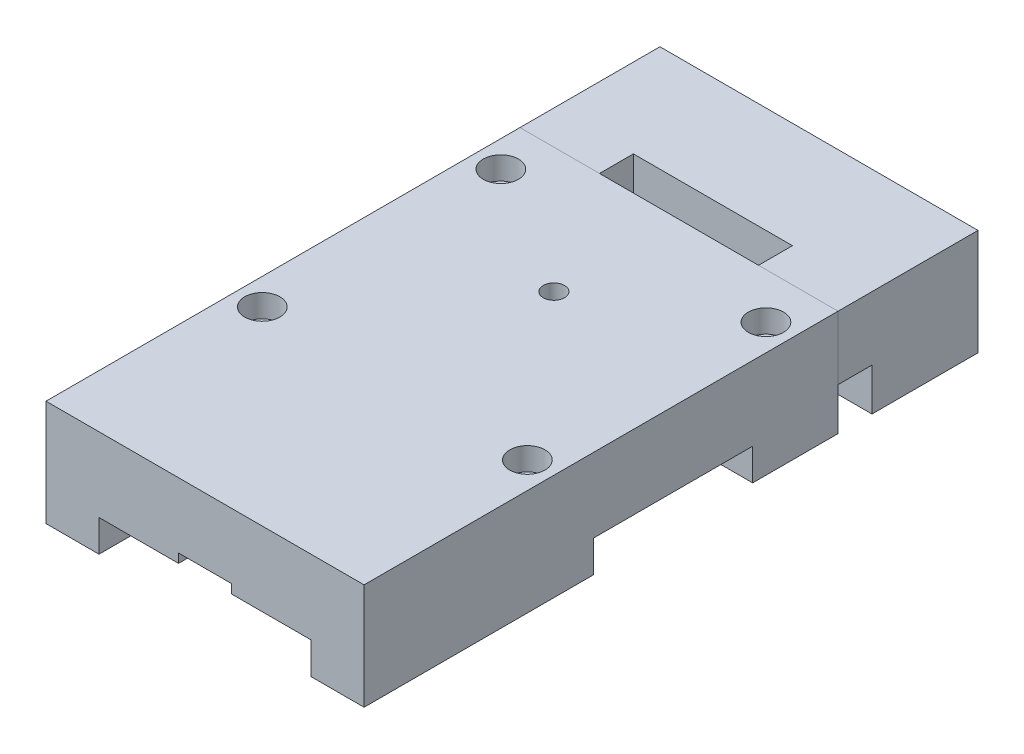
SolidWorks part; units mm, degrees
material "Nylon 6/10"
ref_plane "Front Plane" through (0, 0, 0) normal (0, 0, 1) x (1, 0, 0)
ref_plane "Top Plane" through (0, 0, 0) normal (0, 1, 0) x (1, 0, 0)
ref_plane "Right Plane" through (0, 0, 0) normal (1, 0, 0) x (0, 0, -1)
sketch "Sketch1" plane through (0, 0, 0) normal (0, 1, 0) x (1, 0, 0)
  line L1 (-38.1, -73.533) -> (38.1, -73.533)
  line L2 (-38.1, -73.533) -> (-38.1, 73.533)
  line L3 (-38.1, 73.533) -> (38.1, 73.533)
  line L4 (38.1, -73.533) -> (38.1, 73.533)
  line L5 (-38.1, -73.533) -> (38.1, 73.533) construction
  line L6 (-38.1, 73.533) -> (38.1, -73.533) construction
  point P0 (0, 0)
  dimension "D1" = 76.2
  dimension "D2" = 147.066
extrude "Boss-Extrude1" add sketch "Sketch1" along normal blind 12.7 and the other way blind 12.7
sketch "Sketch2" plane through (0, 0, -73.533) normal (0, 0, -1) x (-1, 0, 0)
  line L1 (-38.1, -12.7) -> (38.1, -12.7) construction
  circle A0 centre (0, -12.7) radius 4.7625
  dimension "D1" = 9.525
extrude "Cut-Extrude1" cut sketch "Sketch2" against normal blind 25.4
ref_plane "Plane1" through (0, -12.7, 0) normal (0, -1, 0) x (-1, 0, 0)
sketch "Sketch3" plane through (0, -12.7, 0) normal (0, -1, 0) x (-1, 0, 0)
  line L0 (10.922, 19.558) -> (44.45, 19.558)
  line L1 (-19.05, -83.058) -> (19.05, -83.058)
  line L2 (-25.4, -76.708) -> (-25.4, -18.542)
  line L3 (0, 0) -> (0, 102.0916) construction
  line L4 (25.4, -76.708) -> (25.4, -18.542)
  line L5 (-10.922, 19.558) -> (-10.922, 40.005)
  line L6 (25.4, -18.542) -> (44.45, -18.542)
  line L7 (-10.922, 40.005) -> (10.922, 40.005)
  line L8 (10.922, 19.558) -> (10.922, 40.005)
  line L10 (-44.45, -18.542) -> (-25.4, -18.542)
  line L11 (-44.45, -18.542) -> (-44.45, 19.558)
  line L12 (-44.45, 19.558) -> (-10.922, 19.558)
  line L13 (44.45, -18.542) -> (44.45, 19.558)
  line L14 (4.7625, 73.533) -> (4.7625, 48.133)
  line L15 (4.7625, 48.133) -> (-4.7625, 48.133)
  line L16 (-4.7625, 48.133) -> (-4.7625, 73.533)
  line L17 (-4.7625, 73.533) -> (-38.1, 73.533)
  line L18 (-38.1, 73.533) -> (-38.1, -73.533)
  line L19 (-38.1, -73.533) -> (38.1, -73.533)
  line L20 (38.1, -73.533) -> (38.1, 73.533)
  line L21 (38.1, 73.533) -> (4.7625, 73.533)
  line L25 (-4.7625, 73.533) -> (-38.1, 73.533) construction
  line L26 (-38.1, 73.533) -> (-38.1, -73.533) construction
  line L27 (-38.1, -73.533) -> (38.1, -73.533) construction
  line L28 (38.1, -73.533) -> (38.1, 73.533) construction
  line L29 (38.1, 73.533) -> (4.7625, 73.533) construction
  arc A0 (-25.4, -76.708) -> (-19.05, -83.058) centre (-19.05, -76.708) ccw
  arc A1 (19.05, -83.058) -> (25.4, -76.708) centre (19.05, -76.708) ccw
  dimension "D5" = 6.35
  dimension "D6" = 21.844
  dimension "D8" = 19.05
  dimension "D9" = 20.447
  dimension "D2" = 25.4
  dimension "D3" = 25.4
  dimension "D4" = 9.525
  dimension "D7" = 38.1
  dimension "D10" = 53.975
  dimension "D1" = 0
extrude "Cut-Extrude2" cut sketch "Sketch3" against normal blind 7.62
sketch "Sketch5" plane through (0, 0, 0) normal (0, 1, 0) x (1, 0, 0)
  line L0 (-4.7625, 73.533) -> (-38.1, 73.533) construction
  line L1 (19.05, 48.133) -> (-19.05, 48.133)
  line L2 (19.05, 40.005) -> (19.05, 48.133)
  line L3 (19.05, 40.005) -> (-19.05, 40.005)
  line L4 (0, 0) -> (0, 121.8983) construction
  line L6 (-19.05, 40.005) -> (-19.05, 48.133)
  point P17 (19.05, 40.005)
  point P20 (19.05, 48.133)
  dimension "D1" = 8.128
  dimension "D2" = 38.1
  dimension "D4" = 25.4
extrude "Cut-Extrude4" cut sketch "Sketch5" along normal through all and the other way through all
hole_wizard "1/4-20 Tapped Hole1" positions "Sketch8" profile "Sketch7" tap size "1/4-20" standard "ANSI Inch"
sketch "Sketch8" plane through (-11.0345, 12.7, 14.5475) normal (0, -1, 0) x (-1, 0, 0)
  line L1 (-30.0845, 62.6805) -> (8.0155, 62.6805) construction
  point P0 (-11.0345, 24.5805)
  dimension "D1" = 38.1
  dimension "D2" = 0
sketch "Sketch7" plane through (0, 12.7, -10.033) normal (1, 0, 0) x (0, 0, 1)
  line L0 (0, 0) -> (0, 20.5838)
  line L1 (0, 20.5838) -> (2.5527, 19.05)
  line L2 (2.5527, 19.05) -> (2.5527, 0)
  line L5 (2.5527, 0) -> (0, 0)
  line L10 (0, 20.5838) -> (-2.5527, 19.05) construction
  line L11 (0, -6.35) -> (0, 107.95) construction
  dimension "Tap Drill Dia." = 5.1054
  dimension "Tap Drill Depth" = 19.05
  dimension "Drill Angle" = 118
cosmetic thread "Hole Thread2" parameters "D1"=9.525, "D2"=6.35
sketch "Sketch9" plane through (0, -12.7, 0) normal (0, -1, 0) x (-1, 0, 0)
  line L0 (38.1, -28.067) -> (25.4, -28.067) construction
  line L1 (38.1, -18.542) -> (38.1, -73.533) construction
  line L2 (25.4, -73.533) -> (25.4, -18.542) construction
  line L3 (25.4, -18.542) -> (38.1, -18.542) construction
  line L4 (38.1, 29.083) -> (25.4, 29.083) construction
  line L5 (38.1, 73.533) -> (38.1, 19.558) construction
  line L6 (-10.922, 19.558) -> (-38.1, 19.558) construction
  line L7 (0, 0) -> (0, 53.9724) construction
  circle A0 centre (31.75, 29.083) radius 2.5527
  circle A1 centre (31.75, -28.067) radius 2.5527
  circle A2 centre (-31.75, -28.067) radius 2.5527
  circle A3 centre (-31.75, 29.083) radius 2.5527
  dimension "D1" = 9.525
  dimension "D2" = 5.1054
  dimension "D3" = 9.525
extrude "Cut-Extrude5" cut sketch "Sketch9" against normal through all
ref_plane "Plane2" through (0, 0, -19.558) normal (0, 0, 1) x (1, 0, 0)
ref_plane "Plane3" through (0, -5.08, 0) normal (0, -1, 0) x (-1, 0, 0)
sketch "Sketch11" plane through (0, -5.08, 0) normal (0, -1, 0) x (-1, 0, 0)
  line L1 (25.4, -73.533) -> (-25.4, -73.533) construction
  line L2 (0.0025, -32.893) -> (-0.0025, -32.893)
  line L3 (6.35, -39.2405) -> (6.35, -73.533)
  line L4 (6.35, -73.533) -> (-6.35, -73.533)
  line L5 (-6.35, -39.2405) -> (-6.35, -73.533)
  line L6 (6.35, -32.893) -> (-6.35, -73.533) construction
  line L7 (6.35, -73.533) -> (-6.35, -32.893) construction
  line L8 (0, -53.213) -> (0, -73.533) construction
  arc A0 (-0.0025, -32.893) -> (-6.35, -39.2405) centre (-0.0025, -39.2405) ccw
  arc A1 (0.0025, -32.893) -> (6.35, -39.2405) centre (0.0025, -39.2405) cw
  point P0 (0, -53.213)
  dimension "D2" = 6.3475
  dimension "D1" = 12.7
  dimension "D3" = 40.64
extrude "Cut-Extrude7" cut sketch "Sketch11" against normal blind 2.159
sketch "Sketch12" plane through (0, -5.08, 0) normal (0, -1, 0) x (1, 0, 0)
  line L0 (0, 0) -> (0, 79.2462) construction
  line L1 (-25.4, 73.533) -> (-6.35, 73.533) construction
  circle A0 centre (12.7, 54.483) radius 2.0193
  circle A1 centre (-12.7, 54.483) radius 2.0193
  dimension "D1" = 4.0386
  dimension "D2" = 25.4
  dimension "D3" = 19.05
extrude "Cut-Extrude8" cut sketch "Sketch12" against normal blind 12.7
sketch "Sketch13" plane through (0, -12.7, 0) normal (0, -1, 0) x (1, 0, 0)
  line L0 (38.1, -19.558) -> (38.1, -73.533) construction
  line L1 (19.05, -40.005) -> (38.1, -40.005)
  line L2 (19.05, -40.005) -> (19.05, -48.133)
  line L3 (19.05, -48.133) -> (38.1, -48.133)
  line L4 (38.1, -40.005) -> (38.1, -48.133)
  line L5 (19.05, -48.133) -> (4.7625, -48.133) construction
extrude "Cut-Extrude9" cut sketch "Sketch13" against normal blind 10.16
ref_plane "Plane4" through (0, 0, -40.005) normal (0, 0, -1) x (-1, 0, 0)
split "Split1" trim tools "Plane4" bodies to split 112 resulting bodies 114 115
sketch "Sketch15" plane through (0, 0, -73.533) normal (0, 0, -1) x (-1, 0, 0)
  line L0 (-38.1, 0) -> (38.1, 0) construction
  line L1 (-38.1, -12.7) -> (-38.1, 12.7) construction
  line L2 (38.1, -12.7) -> (38.1, 12.7) construction
  circle A0 centre (-24.13, 0) radius 2.0193
  circle A1 centre (24.13, 0) radius 2.0193
  dimension "D1" = 4.0386
  dimension "D3" = 13.97
  dimension "D2" = 13.97
extrude "Cut-Extrude11" cut sketch "Sketch15" against normal blind 57.15
sketch "Sketch17" plane through (0, 0, -73.533) normal (0, 0, -1) x (-1, 0, 0)
  line L0 (-38.1, 0) -> (38.1, 0) construction
  line L3 (38.1, -12.7) -> (38.1, 12.7) construction
  circle A0 centre (-24.13, 0) radius 4.2164
  circle A1 centre (24.13, 0) radius 4.2164
  circle A3 centre (24.13, 0) radius 2.0193 construction
  circle A4 centre (-24.13, 0) radius 2.0193 construction
  dimension "D1" = 8.4328
extrude "Cut-Extrude12" cut sketch "Sketch17" against normal blind 5.461
sketch "Sketch18" plane through (0, 12.7, 0) normal (0, 1, 0) x (1, 0, 0)
  circle A0 centre (31.75, -28.067) radius 4.2164
  circle A1 centre (-31.75, -28.067) radius 4.2164
  circle A2 centre (-31.75, 29.083) radius 4.2164
  circle A3 centre (31.75, 29.083) radius 4.2164
  dimension "D1" = 8.4328
extrude "Cut-Extrude13" cut sketch "Sketch18" against normal blind 5.461
sketch "Sketch19" plane through (0, -12.7, 0) normal (0, -1, 0) x (1, 0, 0)
  line L1 (-4.7625, -73.533) -> (-38.1, -73.533) construction
  line L2 (-38.1, -73.533) -> (-38.1, -40.005) construction
  circle A0 centre (-31.75, -57.658) radius 2.0193
  circle A1 centre (-12.7, -57.658) radius 2.0193
  dimension "D1" = 4.0386
  dimension "D2" = 15.875
  dimension "D3" = 6.35
  dimension "D4" = 19.05
extrude "Cut-Extrude14" cut sketch "Sketch19" against normal blind 12.7
sketch "Sketch22" plane through (0, -12.7, 0) normal (0, -1, 0) x (1, 0, 0)
  line L0 (-12.7, -35.1155) -> (12.7, -35.1155) construction
  line L1 (-12.7, -24.4475) -> (12.7, -24.4475) construction
  line L2 (-12.7, -35.9092) -> (12.7, -35.9092)
  line L3 (-12.7, -34.3217) -> (12.7, -34.3217)
  line L4 (-12.7, -23.6537) -> (12.7, -23.6537)
  line L5 (-12.7, -25.2412) -> (12.7, -25.2412)
  line L6 (0, -39.4682) -> (0, -19.7785) construction
  line L7 (10.922, -29.7815) -> (-10.922, -29.7815) construction
  line L10 (10.922, -40.005) -> (10.922, -19.558) construction
  line L11 (-10.922, -19.558) -> (-10.922, -40.005) construction
  arc A0 (-12.7, -23.6537) -> (-12.7, -25.2412) centre (-12.7, -24.4475) ccw
  arc A1 (12.7, -25.2412) -> (12.7, -23.6537) centre (12.7, -24.4475) ccw
  arc A2 (-12.7, -35.9092) -> (-12.7, -34.3217) centre (-12.7, -35.1155) cw
  arc A3 (12.7, -34.3217) -> (12.7, -35.9092) centre (12.7, -35.1155) cw
  point P6 (0, -24.4475)
  point P17 (0, -35.1155)
  dimension "D1" = 1.5875
  dimension "D2" = 25.4
  dimension "D3" = 10.668
extrude "Cut-Extrude16" cut sketch "Sketch22" against normal blind 2.286
sketch "Sketch23" plane through (0, -12.7, 0) normal (0, -1, 0) x (1, 0, 0)
  line L1 (-10.922, -40.005) -> (10.922, -40.005)
  line L2 (-10.922, -40.005) -> (-10.922, -22.733)
  line L3 (-7.747, -19.558) -> (7.747, -19.558)
  line L4 (10.922, -40.005) -> (10.922, -22.733)
  arc A0 (-7.747, -19.558) -> (-10.922, -22.733) centre (-7.747, -22.733) ccw
  arc A1 (7.747, -19.558) -> (10.922, -22.733) centre (7.747, -22.733) cw
  point P9 (10.922, -19.558)
  dimension "D1" = 3.175
extrude "Cut-Extrude18" cut sketch "Sketch23" against normal blind 11.176
